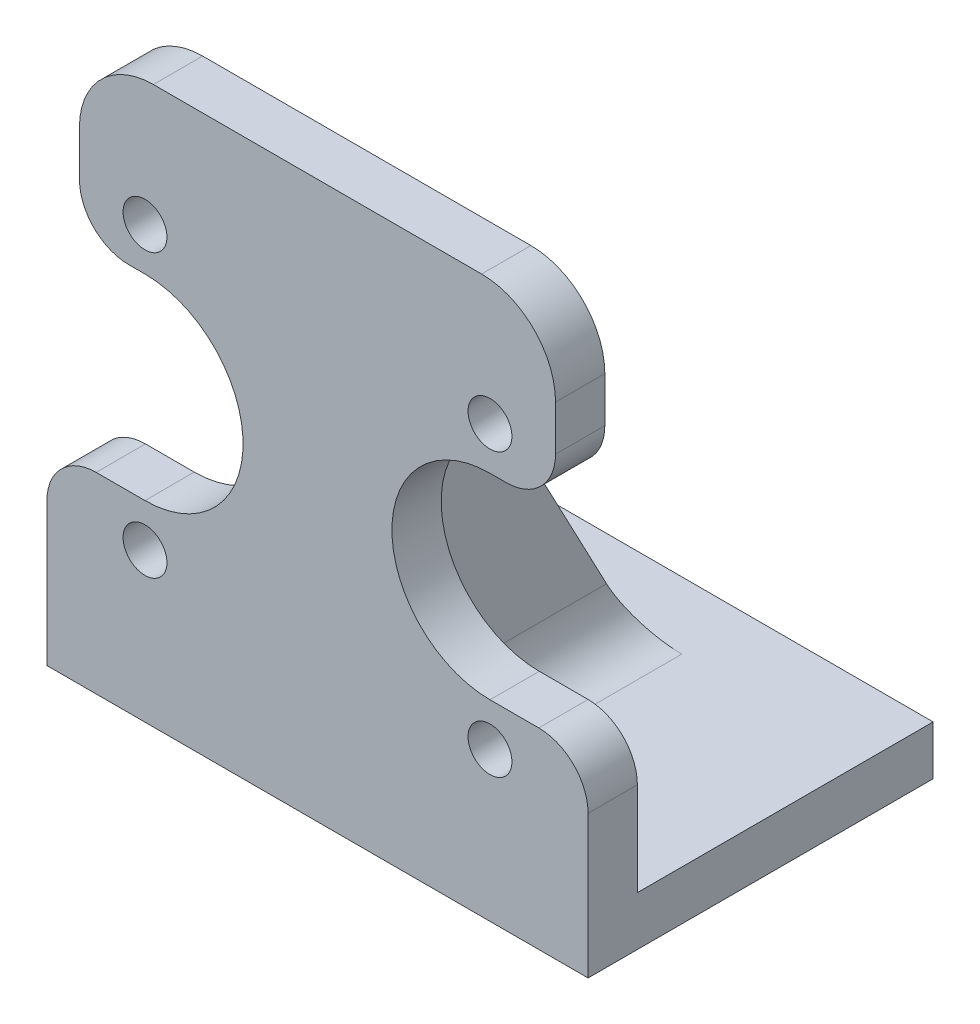
SolidWorks part; units mm, degrees
note: '?' marks a value the reader was unsure of.
ref_plane "Front Plane" through (0, 0, 0) normal (0, 0, 1) x (1, 0, 0)
ref_plane "Top Plane" through (0, 0, 0) normal (0, 1, 0) x (1, 0, 0)
ref_plane "Right Plane" through (0, 0, 0) normal (1, 0, 0) x (0, 0, -1)
sketch "Sketch1" plane through (0, 0, 0) normal (0, 0, 1) x (1, 0, 0)
  line L0 (65, 0) -> (65, -50000) construction
  line L1 (62.03, 0) -> (119.9, 0)
  line L5 (125.4501, 60) -> (62.725, 60) construction
  line L6 (98.2958, 112.8947) -> (31.7042, 112.8947)
  line L7 (16.7042, 97.8947) -> (16.7042, 88.74)
  line L8 (26.7042, 78.74) -> (30, 78.74)
  line L9 (119.9, 28.94) -> (119.9, 0)
  line L10 (30, 38.94) -> (20.1, 38.94)
  line L11 (10.1, 28.94) -> (10.1, 0)
  line L12 (10.1, 0) -> (62.03, 0)
  line L13 (100, 38.94) -> (109.9, 38.94)
  line L14 (103.2958, 78.74) -> (100, 78.74)
  line L15 (113.2958, 97.8947) -> (113.2958, 88.74)
  arc A0 (30, 38.94) -> (30, 78.74) centre (30, 58.84) ccw
  circle A1 centre (30, 30.24) radius 4.45
  circle A2 centre (30, 87.44) radius 4.45
  arc A3 (20.1, 38.94) -> (10.1, 28.94) centre (20.1, 28.94) ccw
  arc A4 (16.7042, 88.74) -> (26.7042, 78.74) centre (26.7042, 88.74) ccw
  arc A5 (31.7042, 112.8947) -> (16.7042, 97.8947) centre (31.7042, 97.8947) ccw
  circle A6 centre (100, 30.24) radius 4.45
  arc A7 (109.9, 38.94) -> (119.9, 28.94) centre (109.9, 28.94) cw
  arc A8 (100, 38.94) -> (100, 78.74) centre (100, 58.84) cw
  circle A9 centre (100, 87.44) radius 4.45
  arc A10 (113.2958, 88.74) -> (103.2958, 78.74) centre (103.2958, 88.74) cw
  arc A11 (98.2958, 112.8947) -> (113.2958, 97.8947) centre (98.2958, 97.8947) cw
  point P46 (65, 112.8947)
  dimension "D3" = 8.9
  dimension "D4" = 39.8
  dimension "D8" = 10
  dimension "D9" = 15
  dimension "D1" = 35
  dimension "D6" = 28.6
  dimension "D7" = 28.6
extrude "Boss-Extrude1" add sketch "Sketch1" against normal blind 10
sketch "Sketch2" plane through (0, 0, 0) normal (1, 0, 0) x (0, 0, -1)
  line L1 (10, 0) -> (70, 0)
  line L2 (10, 0) -> (10, 10)
  line L3 (10, 10) -> (70, 10)
  line L4 (70, 0) -> (70, 10)
  dimension "D1" = 10
  dimension "D2" = 60
extrude "Boss-Extrude2" add sketch "Sketch2" along normal blind 109.8 from offset 10.1
ref_axis "Axis1" through (65, 10, -10) along (0, 0, -1)?
ref_axis "Axis2" through (65, 10, -10) along (0, 1, 0)?
ref_plane "Plane1" through (65, 0, 0) normal (-1, 0, 0) x (0, 0, 1)
sketch "Sketch3" plane through (65, 0, 0) normal (-1, 0, 0) x (0, 0, 1)
  line L0 (-10, 97.8947) -> (-10, 10)
  line L1 (-10, 10) -> (-56.4277, 10)
  line L2 (-10, 10) -> (-70, 10) construction
  line L3 (-56.4277, 10) -> (-10, 97.8947)
extrude "Boss-Extrude3" add sketch "Sketch3" along normal mid plane 15
fillet "Fillet1" radius 10 1 edges at (72.5, 10, -33.2139)
fillet "Fillet2" radius 10 2 edges at (57.5, 10, -33.2139)
